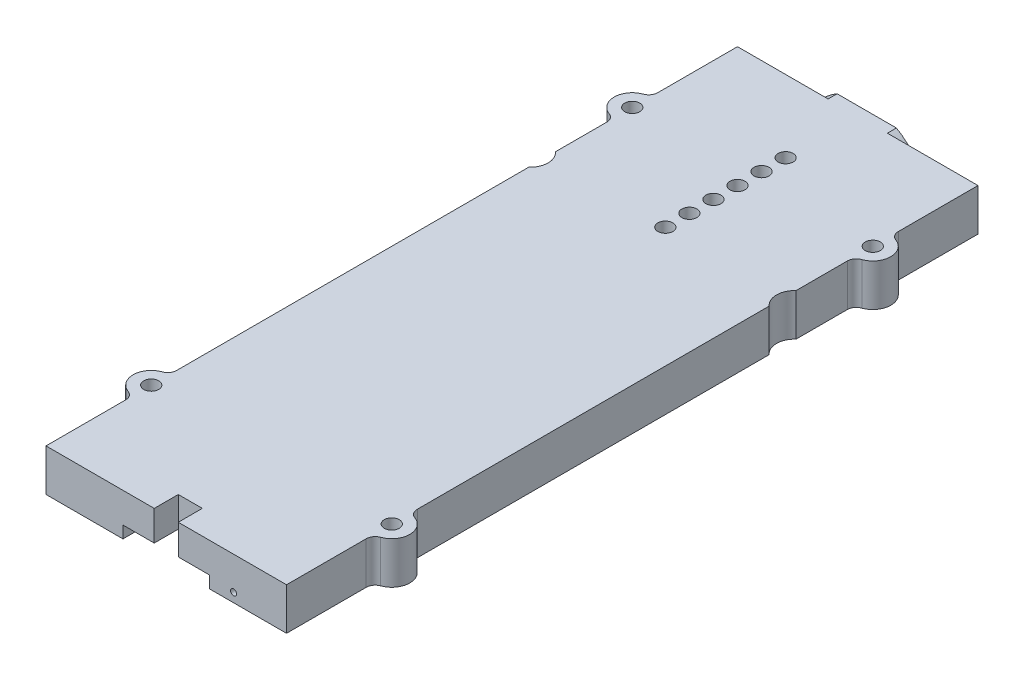
SolidWorks part; units mm, degrees
ref_plane "Спереди" through (0, 0, 0) normal (0, 0, 1) x (1, 0, 0)
ref_plane "Сверху" through (0, 0, 0) normal (0, 1, 0) x (1, 0, 0)
ref_plane "Справа" through (0, 0, 0) normal (1, 0, 0) x (0, 0, -1)
sketch "Эскиз1" plane through (0, 0, 0) normal (0, 1, 0) x (1, 0, 0)
  line L0 (0, 57.5) -> (0, -57.5) construction
  line L1 (-20, 57.5) -> (20, 57.5)
  line L2 (-20, 57.5) -> (-20, -57.5)
  line L3 (-20, -57.5) -> (20, -57.5)
  line L4 (20, 57.5) -> (20, -57.5)
  line L6 (-20, 0) -> (20, 0) construction
  point P8 (0, 0)
  dimension "D1" = 40
  dimension "D2" = 115
extrude "тело" add sketch "Эскиз1" along normal blind 7
sketch "Эскиз2" plane through (0, 7, 0) normal (0, 1, 0) x (1, 0, 0)
  line L0 (-20, 57.5) -> (-20, -57.5) construction
  line L1 (20, -57.5) -> (20, 57.5) construction
  line L2 (0, 57.5) -> (0, -57.5) construction
  line L3 (20, 57.5) -> (-20, 57.5) construction
  line L4 (-20, -57.5) -> (20, -57.5) construction
  line L5 (-20, 37) -> (-20, 43)
  line L6 (20, 43) -> (20, 37)
  line L7 (-20, 40) -> (20, 40) construction
  arc A0 (-20, 43) -> (-20, 37) centre (-20, 40) ccw
  arc A1 (20, 37) -> (20, 43) centre (20, 40) ccw
  dimension "D1" = 3
  dimension "D2" = 40
extrude "наплывы крепления к корпусу" add sketch "Эскиз2" against normal up to surface (7 mm away) up to face at (0, 0, 0)
sketch "Эскиз3" plane through (0, 7, 0) normal (0, 1, 0) x (1, 0, 0)
  circle A0 centre (-20, 40) radius 1.25
  circle A1 centre (20, 40) radius 1.25
  dimension "D1" = 2.5
extrude "крепежные отверстия" cut sketch "Эскиз3" against normal through all
mirror "Зеркальное отражение1" about plane through (0, 0, 0) normal (0, 0, 1) of "наплывы крепления к корпусу", "крепежные отверстия"
sketch "Эскиз4" plane through (0, 0, 0) normal (0, -1, 0) x (1, 0, 0)
  line L0 (15, 52.5) -> (-15, -52.5) construction
  line L1 (-15, 52.5) -> (15, 52.5)
  line L2 (-15, 52.5) -> (-15, -52.5)
  line L3 (-15, -52.5) -> (15, -52.5)
  line L4 (15, 52.5) -> (15, -52.5)
  line L5 (0, 57.5) -> (0, -57.5) construction
  line L6 (-20, 57.5) -> (20, 57.5) construction
  line L7 (20, -57.5) -> (-20, -57.5) construction
  line L8 (-2, -25.5) -> (-2, -45.5)
  line L9 (-20, -37) -> (-20, 37) construction
  line L10 (-20, 0) -> (20, 0) construction
  line L11 (20, 37) -> (20, -37) construction
  line L13 (2, -25.5) -> (2, -45.5)
  arc A0 (2, -25.5) -> (-2, -25.5) centre (0, -25.5) ccw
  arc A1 (-2, -45.5) -> (2, -45.5) centre (0, -45.5) ccw
  point P13 (0, 0)
  dimension "D3" = 2
  dimension "D1" = 30
  dimension "D2" = 105
  dimension "D4" = 20
  dimension "D5" = 7
extrude "вырез под плату" cut sketch "Эскиз4" against normal blind 4
sketch "Эскиз5" plane through (0, 0, 0) normal (0, -1, 0) x (1, 0, 0)
  line L0 (-20, 57.5) -> (20, 57.5) construction
  line L1 (-7.2, 0) -> (7.2, 0)
  line L2 (-7.2, 0) -> (-7.2, 57.5)
  line L3 (-7.2, 57.5) -> (7.2, 57.5)
  line L4 (7.2, 0) -> (7.2, 57.5)
  point P4 (0, 0)
  dimension "D1" = 14.4
extrude "вырез под rj45" cut sketch "Эскиз5" against normal blind 2
sketch "Эскиз6" plane through (0, 2, 0) normal (0, -1, 0) x (1, 0, 0)
  line L0 (7.2, 57.5) -> (-7.2, 57.5) construction
  line L1 (-2, 57.5) -> (2, 57.5)
  line L2 (-2, 57.5) -> (-2, 53.5)
  line L3 (-2, 53.5) -> (2, 53.5)
  line L4 (2, 57.5) -> (2, 53.5)
  point P4 (0, 57.5)
  point P7 (0, 57.5)
  dimension "D1" = 4
extrude "вырез под ушко rj45" cut sketch "Эскиз6" against normal through all
sketch "Эскиз7" plane through (0, 0, 0) normal (0, -1, 0) x (1, 0, 0)
  line L0 (-15, -52.5) -> (15, -52.5) construction
  line L1 (-5, -52.5) -> (5, -52.5)
  line L2 (-5, -52.5) -> (-5, -57.5)
  line L3 (-5, -57.5) -> (5, -57.5)
  line L4 (5, -52.5) -> (5, -57.5)
  line L5 (20, -57.5) -> (-20, -57.5) construction
  point P4 (0, -52.5)
  point P7 (0, -52.5)
  dimension "D1" = 10
extrude "вырез под sma" cut sketch "Эскиз7" against normal blind 3
sketch "Эскиз8" plane through (0, 0, -57.5) normal (0, 0, -1) x (-1, 0, 0)
  line L0 (0, 7) -> (0, 0) construction
  line L1 (-20, 7) -> (20, 7) construction
  line L2 (-20, 0) -> (-5, 0) construction
  line L3 (-4.9305, 7) -> (4.9305, 7)
  line L4 (-9.8544, 0) -> (-2.4718, 0)
  line L5 (2.4718, 0) -> (9.8544, 0)
  line L6 (5, 0) -> (20, 0) construction
  arc A0 (-4.9305, 7) -> (-9.8544, 0) centre (0, -1.7) ccw
  arc A1 (2.4718, 0) -> (-2.4718, 0) centre (0, -1.7) ccw
  arc A2 (9.8544, 0) -> (4.9305, 7) centre (0, -1.7) ccw
  dimension "D1" = 1.7
  dimension "D2" = 6
  dimension "D3" = 20
extrude "наплыв под sma" add sketch "Эскиз8" along normal blind 1.5
sketch "Эскиз9" plane through (0, 0, 0) normal (0, -1, 0) x (1, 0, 0)
  line L0 (7.2, 52.5) -> (15, 52.5)
  line L1 (7.2, 52.5) -> (7.2, 54.5)
  line L2 (15, 52.5) -> (15, 54.5)
  line L3 (7.2, 54.5) -> (15, 54.5)
  dimension "D1" = 2
extrude "вырез под reset" cut sketch "Эскиз9" against normal up to surface (2 mm away) up to face at (0, 2, 55.25)
sketch "Эскиз10" plane through (0, 7, 0) normal (0, 1, 0) x (1, 0, 0)
  line L0 (0, 59) -> (0, -53.5) construction
  line L1 (-4.9305, 59) -> (4.9305, 59) construction
  line L2 (-2, -53.5) -> (2, -53.5) construction
  line L3 (-22, 25) -> (22, 25) construction
  line L4 (-20, 0) -> (20, 0) construction
  line L5 (-20, 37) -> (-20, -37) construction
  line L6 (20, -37) -> (20, 37) construction
  circle A0 centre (-22, 25) radius 3
  circle A1 centre (22, 25) radius 3
  dimension "D1" = 6
  dimension "D2" = 44
  dimension "D3" = 25
extrude "вырез под шляпки болтов" cut sketch "Эскиз10" against normal through all
mirror "Зеркальное отражение2" [suppressed] about plane through (0, 0, 0) normal (0, 0, 1)
sketch "Эскиз11" plane through (0, 0, 0) normal (0, -1, 0) x (1, 0, 0)
  circle A0 centre (0, -45.5) radius 1.25
  dimension "D1" = 2.5
extrude "отверстие под светодиод" cut sketch "Эскиз11" against normal through all
pattern_linear "Линейный массив1" count 6 spacing 4 along (0, 0, 1) of "отверстие под светодиод"
sketch "Эскиз12" plane through (0, 0, 57.5) normal (0, 0, 1) x (1, 0, 0)
  line L0 (7.2, 2) -> (20, 2) construction
  line L1 (20, 7) -> (20, 0) construction
  line L2 (7.2, 2) -> (7.2, 0) construction
  circle A0 centre (11.2, 1.5) radius 0.5
  dimension "D1" = 1
  dimension "D2" = 4
extrude "отверстие под reset" cut sketch "Эскиз12" against normal up to surface (3 mm away) up to face at (11.1, 1, 54.5)
fillet "Скругление1" radius 1.5 8 edges at (-20, 3.5, 43) (-20, 3.5, 37) (-20, 3.5, -37) (-20, 3.5, -43) (20, 3.5, -43) (20, 3.5, -37) (20, 3.5, 37) (20, 3.5, 43)
